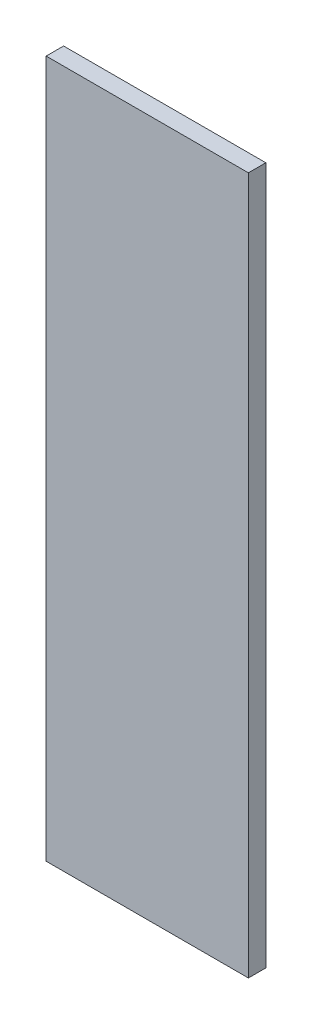
SolidWorks part; units mm, degrees
ref_plane "Plan de face" through (0, 0, 0) normal (0, 0, 1) x (1, 0, 0)
ref_plane "Plan de dessus" through (0, 0, 0) normal (0, 1, 0) x (1, 0, 0)
ref_plane "Plan de droite" through (0, 0, 0) normal (1, 0, 0) x (0, 0, -1)
sketch "Esquisse1" plane through (0, 0, 0) normal (0, 0, 1) x (1, 0, 0)
  line L1 (29, -100) -> (-29, -100)
  line L2 (29, -100) -> (29, 100)
  line L3 (29, 100) -> (-29, 100)
  line L4 (-29, -100) -> (-29, 100)
  line L5 (29, -100) -> (-29, 100) construction
  line L6 (29, 100) -> (-29, -100) construction
  point P0 (0, 0)
  dimension "D1" = 58
  dimension "D2" = 200
base flange "Tôle de base pliée1" sketch "Esquisse1" thickness 5 reverse thickness direction no parameters "D1"=0.7366
sketch "Lignes de pliage1" [suppressed] plane through (0, 0, 0) normal (0, 1, 0) x (1, 0, 0)
sketch "Cube de visualisation1" [suppressed] plane through (0, 0, 0) normal (0, 1, 0) x (1, 0, 0)
sheet metal parameters "Tôlerie1" thickness 5 parameters "D1"=0.7366
flat pattern "Etat déplié1" [suppressed]
sketch "Lignes de pliage2" plane through (0, 0, 0) normal (0, 1, 0) x (1, 0, 0)
sketch3d "Cube de visualisation2" [suppressed]
  line L0 (29, 100, 0) -> (29, -100, 0) construction
  line L1 (-29, 100, 0) -> (-29, -100, 0) construction
  line L2 (29, 100, 0) -> (-29, 100, 0) construction
  line L3 (29, -100, 0) -> (-29, -100, 0) construction
